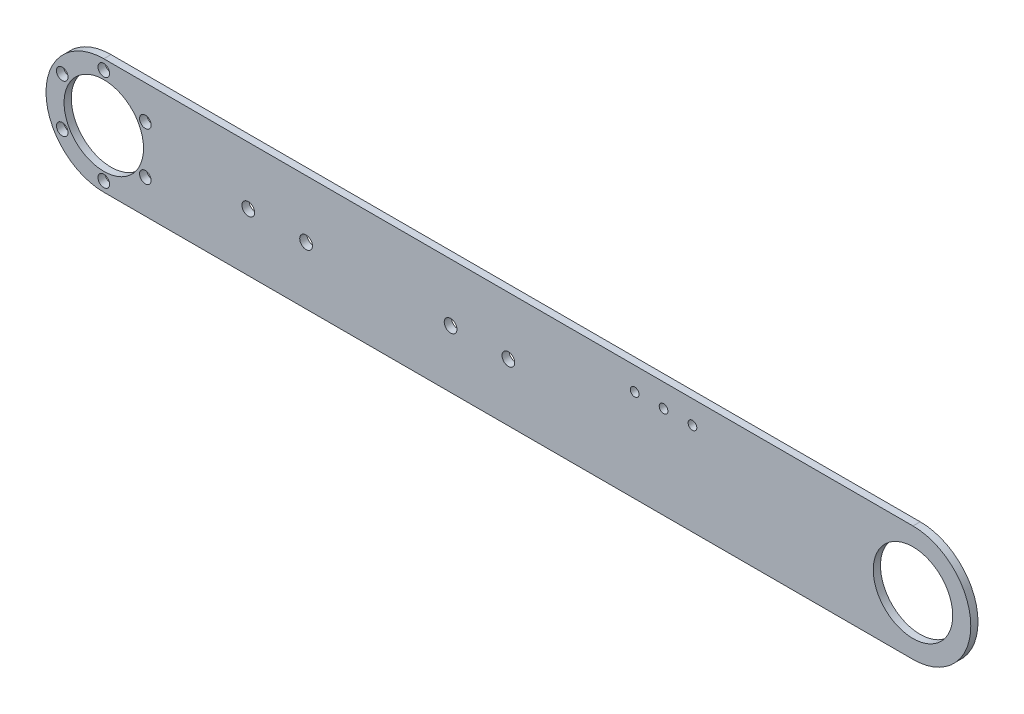
SolidWorks part; units mm, degrees
ref_plane "Front Plane" through (0, 0, 0) normal (0, 0, 1) x (1, 0, 0)
ref_plane "Top Plane" through (0, 0, 0) normal (0, 1, 0) x (1, 0, 0)
ref_plane "Right Plane" through (0, 0, 0) normal (1, 0, 0) x (0, 0, -1)
sketch "Sketch1" plane through (0, 0, 0) normal (0, 0, 1) x (1, 0, 0)
  line L1 (0, 0) -> (355.6, 0)
  line L3 (0, 50.8) -> (355.6, 50.8)
  arc A0 (0, 50.8) -> (0, 0) centre (0, 25.4) ccw
  arc A1 (355.6, 0) -> (355.6, 50.8) centre (355.6, 25.4) ccw
  dimension "D1" = 355.6
  dimension "D2" = 50.8
extrude "Boss-Extrude1" add sketch "Sketch1" along normal blind 3.175
sketch "Sketch2" plane through (0, 0, 3.175) normal (0, 0, 1) x (1, 0, 0)
  circle A0 centre (0, 25.4) radius 17.4625
  arc A1 (0, 50.8) -> (0, 0) centre (0, 25.4) ccw construction
  circle A3 centre (355.6, 25.4) radius 17.4625
  arc A5 (355.6, 0) -> (355.6, 50.8) centre (355.6, 25.4) ccw construction
  dimension "D1" = 34.925
  dimension "D2" = 34.925
extrude "Cut-Extrude1" cut sketch "Sketch2" against normal through all
sketch "Sketch4" plane through (0, 0, 3.175) normal (0, 0, 1) x (1, 0, 0)
  point P0 (0, 46.482)
  point P4 (0, 25.4)
  point P5 (18.2575, 35.941)
  point P7 (18.2575, 14.859)
  point P8 (0, 4.318)
  point P9 (-18.2575, 14.859)
  point P10 (-18.2575, 35.941)
  point P11 (0, 25.4)
  dimension "D1" = 21.082
  dimension "D2" = 6
hole_wizard "#10 Clearance Hole1" positions "3DSketch2" profile "Sketch5" hole size "#10" standard "ANSI Inch" end condition through all
sketch3d "3DSketch2"
  point P0 (18.2575, 35.941, 3.175)
  point P3 (18.2575, 14.859, 3.175)
  point P6 (0, 4.318, 3.175)
  point P9 (-18.2575, 14.859, 3.175)
  point P12 (-18.2575, 35.941, 3.175)
  point P15 (0, 46.482, 3.175)
sketch "Sketch5" plane through (18.2575, 35.941, 3.175) normal (1, 0, 0) x (0, -1, 0)
  line L0 (0, 0) -> (0, 3.175)
  line L1 (0, 3.175) -> (2.5527, 3.175)
  line L2 (2.5527, 3.175) -> (2.5527, 0)
  line L5 (2.5527, 0) -> (0, 0)
  line L11 (0, -6.35) -> (0, 107.95) construction
  dimension "Thru Hole Dia." = 5.1054
  dimension "Thru Hole Depth" = 3.175
ref_axis "Axis1" through (177.8, 50.8, 0) along (0, -0.9981, 0.0624)
ref_plane "Plane1" through (177.8, 0, 0) normal (1, 0, 0) x (0, 0, -1)
sketch "Sketch6" plane through (0, 0, 3.175) normal (0, 0, 1) x (1, 0, 0)
  line L0 (0, 25.4) -> (262.6971, 25.4) construction
  circle A0 centre (63.5, 25.4) radius 2.794
  circle A1 centre (88.9, 25.4) radius 2.794
  circle A2 centre (152.4, 25.4) radius 2.794
  circle A3 centre (177.8, 25.4) radius 2.794
  arc A4 (-10.0823, 2.0868) -> (10.0823, 48.7132) centre (0, 25.4) ccw construction
  dimension "D1" = 5.588
  dimension "D2" = 25.4
  dimension "D3" = 25.4
  dimension "D4" = 63.5
  dimension "D5" = 63.5
extrude "Cut-Extrude2" cut sketch "Sketch6" against normal through all
sketch "Sketch7" plane through (0, 0, 3.175) normal (0, 0, 1) x (1, 0, 0)
  line L0 (355.6, 50.8) -> (0, 50.8) construction
  circle A0 centre (258.6877, 40.64) radius 1.905
  circle A1 centre (245.9877, 40.64) radius 1.905
  circle A2 centre (233.2877, 40.64) radius 1.905
  point P6 (0, 0)
  point P9 (234.6367, 40.64)
  point P10 (229.3334, 40.64)
  point P11 (233.2877, 40.64)
  dimension "D1" = 3.81
  dimension "D2" = 12.7
  dimension "D3" = 12.7
  dimension "D4" = 10.16
extrude "Cut-Extrude3" cut sketch "Sketch7" against normal through all
